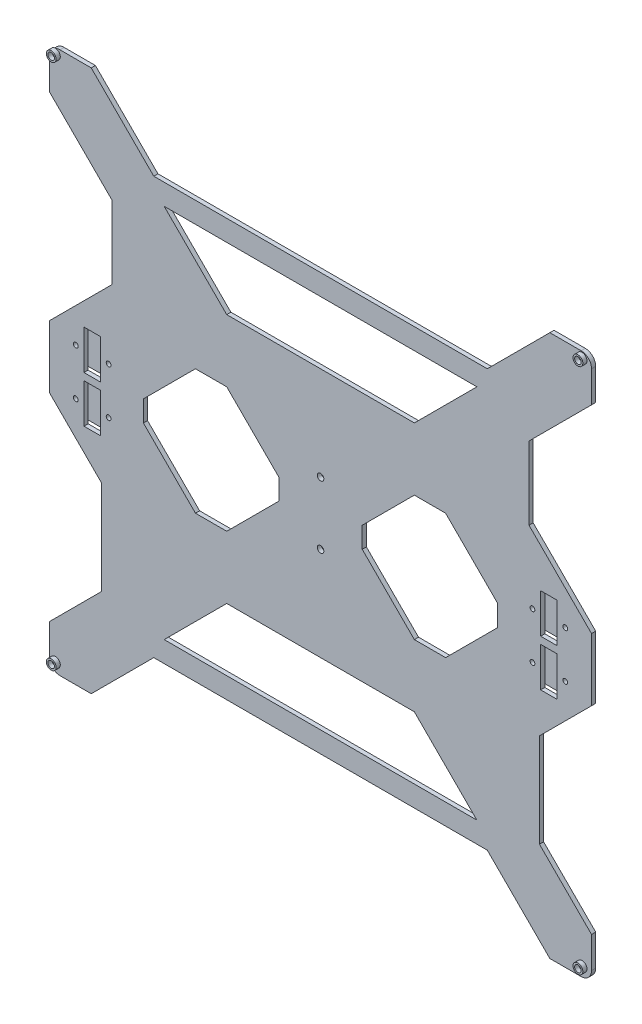
SolidWorks part; units mm, degrees
ref_plane "Front Plane" through (0, 0, 0) normal (0, 0, 1) x (1, 0, 0)
ref_plane "Top Plane" through (0, 0, 0) normal (0, 1, 0) x (1, 0, 0)
ref_plane "Right Plane" through (0, 0, 0) normal (1, 0, 0) x (0, 0, -1)
sketch "Model" plane through (0, 0, 0) normal (0, 0, 1) x (1, 0, 0)
  line L0 (38.5361, 132.6139) -> (38.5361, 132.4727)
  line L1 (38.5361, -178.6774) -> (38.5361, -178.7219)
  line L2 (-253.5639, -197.5861) -> (-253.5639, -197.7273)
  line L3 (-252.5813, 70.3317) -> (-252.5813, 25.8817)
  line L4 (-258.9313, -82.0683) -> (-258.9313, -139.2183)
  line L5 (38.5361, 132.6139) -> (38.5361, 132.4727)
  line L6 (38.5361, -178.6774) -> (38.5361, -178.7219)
  line L7 (7.7687, -139.2183) -> (7.7687, -82.0683)
  line L8 (1.4187, 25.8817) -> (1.4187, 70.3317)
  line L9 (-23.9813, 95.7317) -> (-227.1813, 95.7317)
  line L10 (-290.6813, 108.4317) -> (-252.5813, 70.3317)
  line L11 (-30.3313, -145.5683) -> (-68.4313, -107.4683)
  line L12 (-23.9813, -158.2683) -> (14.1187, -196.3683)
  line L13 (39.5187, 108.4317) -> (39.5187, 127.4817)
  line L14 (-227.1813, 95.7317) -> (-265.2813, 133.8317)
  line L15 (-220.8313, 83.0317) -> (-182.7313, 44.9317)
  line L16 (-274.6813, -45.4288) -> (-254.6813, -45.4288) construction
  line L17 (39.5187, -170.9683) -> (7.7687, -139.2183)
  line L18 (-265.2813, -196.3683) -> (-227.1813, -158.2683)
  line L19 (-182.7313, -107.4683) -> (-68.4313, -107.4683)
  line L20 (-264.6813, -45.4288) -> (-264.6813, -43.5832) construction
  line L21 (1.4187, 70.3317) -> (39.5187, 108.4317)
  line L22 (-23.9813, 95.7317) -> (14.1187, 133.8317)
  line L23 (-30.3313, 83.0317) -> (-68.4313, 44.9317)
  line L25 (-258.9313, -139.2183) -> (-290.6813, -170.9683)
  line L26 (-182.7313, 44.9317) -> (-68.4313, 44.9317)
  line L27 (-220.8313, -145.5683) -> (-182.7313, -107.4683)
  line L28 (-220.8313, -145.5683) -> (-30.3313, -145.5683)
  line L29 (-258.9313, -82.0683) -> (-290.6813, -50.3183)
  line L30 (-290.6813, -12.2183) -> (-290.6813, -50.3183)
  line L31 (-274.6813, -43.9683) -> (-274.6813, -31.2683) construction
  line L32 (-290.6813, -12.2183) -> (-252.5813, 25.8817)
  line L33 (-201.7813, -69.3683) -> (-233.5313, -37.6183)
  line L34 (-182.7313, -69.3683) -> (-201.7813, -69.3683)
  line L35 (1.4187, 25.8817) -> (39.5187, -12.2183)
  line L36 (39.5187, -12.2183) -> (39.5187, -50.3183)
  line L37 (-150.9813, -37.6183) -> (-182.7313, -69.3683)
  line L38 (39.5187, -50.3183) -> (22.4579, -67.3791)
  line L39 (22.4579, -67.3791) -> (7.7687, -82.0683)
  line L40 (-100.1813, -37.6183) -> (-100.1813, -24.9183)
  line L41 (-150.9813, -37.6183) -> (-150.9813, -24.9183)
  line L42 (-150.9813, -24.9183) -> (-182.7313, 6.8317)
  line L43 (-182.7313, 6.8317) -> (-201.7813, 6.8317)
  line L44 (-201.7813, 6.8317) -> (-233.5313, -24.9183)
  line L45 (-233.5313, -24.9183) -> (-233.5313, -37.6183)
  line L46 (-17.6313, -24.9183) -> (-17.6313, -37.6183)
  line L47 (-49.3813, 6.8317) -> (-17.6313, -24.9183)
  line L48 (-220.8313, 83.0317) -> (-30.3313, 83.0317)
  line L49 (-68.4313, 6.8317) -> (-49.3813, 6.8317)
  line L50 (-100.1813, -24.9183) -> (-68.4313, 6.8317)
  line L51 (-100.1813, -37.6183) -> (-68.4313, -69.3683)
  line L52 (-68.4313, -69.3683) -> (-49.3813, -69.3683)
  line L53 (-49.3813, -69.3683) -> (-17.6313, -37.6183)
  line L58 (-265.2813, -196.3683) -> (-284.3313, -196.3683)
  line L59 (-290.6813, -190.0183) -> (-290.6813, -170.9683)
  line L60 (-290.6813, 108.4317) -> (-290.6813, 127.4817)
  line L61 (-284.3313, 133.8317) -> (-265.2813, 133.8317)
  line L62 (14.1187, 133.8317) -> (33.1687, 133.8317)
  line L64 (39.5187, -170.9683) -> (39.5187, -190.0183)
  line L65 (33.1687, -196.3683) -> (14.1187, -196.3683)
  line L71 (-227.1813, -158.2683) -> (-23.9813, -158.2683)
  line L72 (38.5361, -178.6774) -> (38.5361, -178.7219)
  line L74 (-227.1813, -158.2683) -> (-23.9813, -158.2683)
  line L75 (38.5361, -178.6774) -> (38.5361, -178.7219)
  line L77 (-125.5813, 95.7317) -> (-125.5813, -158.2683) construction
  line L78 (-290.6813, -31.2683) -> (39.5187, -31.2683) construction
  arc A0 (33.1687, -196.3683) -> (39.5187, -190.0183) centre (33.1687, -190.0183) ccw
  arc A1 (-290.6813, -190.0183) -> (-284.3313, -196.3683) centre (-284.3313, -190.0183) ccw
  arc A2 (-290.6813, 127.4817) -> (-284.3313, 133.8317) centre (-284.3313, 127.4817) cw
  arc A3 (33.1687, 133.8317) -> (39.5187, 127.4817) centre (33.1687, 127.4817) cw
  circle A4 centre (-287.1253, -190.6025) radius 1.4605
  circle A5 centre (33.7529, -190.6025) radius 1.4605
  circle A6 centre (33.7529, 130.2757) radius 1.4605
  circle A7 centre (-287.1253, 130.2757) radius 1.4605
  circle A8 centre (-274.6813, -45.4288) radius 1.4605
  circle A9 centre (-254.6813, -45.4288) radius 1.4605
  circle A10 centre (23.5187, -45.4288) radius 1.4605
  circle A11 centre (3.5187, -45.4288) radius 1.4605
  circle A12 centre (23.5187, -17.1078) radius 1.4605
  circle A13 centre (3.5187, -17.1078) radius 1.4605
  circle A14 centre (-254.6813, -17.1078) radius 1.4605
  circle A15 centre (-274.6813, -17.1078) radius 1.4605
  circle A16 centre (-125.5813, -12.2183) radius 2
  circle A17 centre (-125.5813, -50.3183) radius 2
  point P72 (-125.5813, -31.2683)
  point P79 (-290.6813, -31.2683)
  point P114 (-125.5813, 83.0317)
  point P116 (39.5187, -31.2683)
  point P120 (-233.5313, -31.2683)
  point P129 (-150.9813, -31.2683)
  point P141 (-290.6813, -180.4933)
  point P149 (-125.5813, 44.9317)
  point P156 (-17.6313, -31.2683)
  dimension "D28" = 6.35
  dimension "D29" = 6.35
  dimension "D30" = 6.35
  dimension "D31" = 6.35
  dimension "D35" = 2.921
  dimension "D36" = 2.921
  dimension "D37" = 2.921
  dimension "D38" = 2.921
  dimension "D53" = 2.921
  dimension "D54" = 2.921
  dimension "D56" = 4
  dimension "D57" = 4
  dimension "D1" = 330.2
  dimension "D2" = 330.2
  dimension "D3" = 135
  dimension "D4" = 135
  dimension "D5" = 38.1
  dimension "D6" = 135
  dimension "D7" = 135
  dimension "D8" = 19.05
  dimension "D9" = 135
  dimension "D10" = 19.05
  dimension "D11" = 31.75
  dimension "D12" = 190.5
  dimension "D13" = 114.3
  dimension "D14" = 38.1
  dimension "D15" = 114.3
  dimension "D16" = 135
  dimension "D17" = 6.35
  dimension "D18" = 38.1
  dimension "D19" = 135
  dimension "D20" = 135
  dimension "D21" = 6.35
  dimension "D22" = 19.05
  dimension "D23" = 25.4
  dimension "D24" = 38.1
  dimension "D25" = 135
  dimension "D26" = 135
  dimension "D27" = 127
  dimension "D32" = 19.05
  dimension "D33" = 19.05
  dimension "D34" = 19.05
  dimension "D39" = 38.1
  dimension "D40" = 19.05
  dimension "D41" = 38.1
  dimension "D42" = 38.1
  dimension "D43" = 135
  dimension "D44" = 19.05
  dimension "D45" = 31.75
  dimension "D46" = 135
  dimension "D47" = 320.8782
  dimension "D48" = 320.8782
  dimension "D49" = 3.556
  dimension "D50" = 3.556
  dimension "D51" = 20
  dimension "D52" = 26
  dimension "D55" = 12.7
  dimension "D58" = 38.1
  dimension "D59" = 19.05
extrude "Boss-Extrude1" add sketch "Model" along normal mid plane 2.54 contours A3 L62 L22 L9 L14 L61 A2 L60 L10 L3 L32 L30 L29 L4 L25 L59 A1 L58 L18 L71 L12 L65 A0 L64 L17 L7 L39 L38 L36 L35 L8 L21 L13 A17 A16 A14 A13 A12 A10 A9 region at (-125.5808, -32.1456, 0)
sketch "Sketch1" plane through (0, 0, 1.27) normal (0, 0, 1) x (1, 0, 0)
  line L1 (-269.6813, -33.4288) -> (-259.6813, -33.4288)
  line L2 (-269.6813, -33.4288) -> (-269.6813, -57.4288)
  line L3 (-269.6813, -57.4288) -> (-259.6813, -57.4288)
  line L4 (-259.6813, -33.4288) -> (-259.6813, -57.4288)
  line L5 (-269.6813, -5.1078) -> (-259.6813, -5.1078)
  line L6 (-269.6813, -5.1078) -> (-269.6813, -29.1078)
  line L7 (-269.6813, -29.1078) -> (-259.6813, -29.1078)
  line L8 (-259.6813, -5.1078) -> (-259.6813, -29.1078)
  line L9 (8.5187, -5.1078) -> (18.5187, -5.1078)
  line L10 (8.5187, -5.1078) -> (8.5187, -29.1078)
  line L11 (8.5187, -29.1078) -> (18.5187, -29.1078)
  line L12 (18.5187, -5.1078) -> (18.5187, -29.1078)
  line L13 (8.5187, -33.4288) -> (18.5187, -33.4288)
  line L14 (8.5187, -33.4288) -> (8.5187, -57.4288)
  line L15 (8.5187, -57.4288) -> (18.5187, -57.4288)
  line L16 (18.5187, -33.4288) -> (18.5187, -57.4288)
  circle A1 centre (-274.6813, -45.4288) radius 1.4605 construction
  circle A5 centre (-274.6813, -17.1078) radius 1.4605 construction
  circle A7 centre (-254.6813, -17.1078) radius 1.4605 construction
  circle A8 centre (23.5187, -17.1078) radius 1.4605 construction
  circle A9 centre (23.5187, -45.4288) radius 1.4605 construction
  dimension "D3" = 12
  dimension "D4" = 5
  dimension "D5" = 10
  dimension "D8" = 12
  dimension "D11" = 12
  dimension "D15" = 12
  dimension "D1" = 10
  dimension "D2" = 24
  dimension "D6" = 24
  dimension "D7" = 5
  dimension "D9" = 24
  dimension "D10" = 5
  dimension "D12" = 10
  dimension "D13" = 10
  dimension "D14" = 24
  dimension "D16" = 5
extrude "Cut-Extrude1" cut sketch "Sketch1" against normal blind 10
sketch "Sketch2" plane through (0, 0, 1.27) normal (0, 0, 1) x (1, 0, 0)
  circle A0 centre (33.7529, -190.6025) radius 3
  circle A1 centre (33.7529, -190.6025) radius 2
  circle A2 centre (-287.1253, -190.6025) radius 2
  circle A3 centre (-287.1253, -190.6025) radius 3
  circle A4 centre (-287.1253, 130.2757) radius 2
  circle A5 centre (-287.1253, 130.2757) radius 3
  circle A6 centre (33.7529, 130.2757) radius 2
  circle A7 centre (33.7529, 130.2757) radius 3
  dimension "D1" = 6
  dimension "D2" = 4
extrude "Boss-Extrude2" add sketch "Sketch2" along normal blind 2.54
sketch "Sketch3" plane through (0, 0, -1.27) normal (0, 0, -1) x (-1, 0, 0)
  line L0 (264.6813, -5.1078) -> (264.6813, -17.1078) construction
  line L1 (254.6813, -7.1078) -> (274.6813, -7.1078)
  line L2 (254.6813, -7.1078) -> (254.6813, -27.1078)
  line L3 (254.6813, -27.1078) -> (274.6813, -27.1078)
  line L4 (274.6813, -7.1078) -> (274.6813, -27.1078)
  line L5 (254.6813, -7.1078) -> (274.6813, -27.1078) construction
  line L6 (254.6813, -27.1078) -> (274.6813, -7.1078) construction
  line L7 (254.6813, -27.1078) -> (274.6813, -27.1078)
  line L12 (254.6813, -35.4288) -> (274.6813, -35.4288)
  line L13 (113.0267, 3.6533) -> (134.9991, 3.6533)
  line L14 (113.0267, 3.6533) -> (113.0267, -64.6419)
  line L15 (113.0267, -64.6419) -> (134.9991, -64.6419)
  line L16 (134.9991, 3.6533) -> (134.9991, -64.6419)
  line L17 (113.0267, 3.6533) -> (134.9991, -64.6419) construction
  line L18 (113.0267, -64.6419) -> (134.9991, 3.6533) construction
  line L19 (-23.5187, -7.1078) -> (-3.5187, -7.1078)
  line L20 (-23.5187, -7.1078) -> (-23.5187, -27.1078)
  line L22 (-3.5187, -7.1078) -> (-3.5187, -27.1078)
  line L23 (-23.5187, -7.1078) -> (-3.5187, -27.1078) construction
  line L24 (-23.5187, -27.1078) -> (-3.5187, -7.1078) construction
  line L29 (-3.5187, -27.1078) -> (-23.5187, -27.1078)
  line L30 (254.6813, -35.4288) -> (254.6813, -55.4288)
  line L31 (259.6813, -5.1078) -> (269.6813, -5.1078) construction
  line L32 (264.6813, -17.1078) -> (269.6813, -17.1078) construction
  line L33 (269.6813, -5.1078) -> (269.6813, -29.1078) construction
  line L34 (264.6813, -33.4288) -> (264.6813, -45.4288) construction
  line L35 (259.6813, -33.4288) -> (269.6813, -33.4288) construction
  line L36 (264.6813, -45.4288) -> (269.6813, -45.4288) construction
  line L37 (269.6813, -33.4288) -> (269.6813, -57.4288) construction
  line L38 (-13.5187, -5.1078) -> (-13.5187, -17.1078) construction
  line L39 (-18.5187, -5.1078) -> (-8.5187, -5.1078) construction
  line L40 (-13.5187, -17.1078) -> (-8.5187, -17.1078) construction
  line L41 (-8.5187, -5.1078) -> (-8.5187, -29.1078) construction
  line L42 (-13.5187, -33.4288) -> (-13.5187, -45.4288) construction
  line L43 (-18.5187, -33.4288) -> (-8.5187, -33.4288) construction
  line L44 (-13.5187, -45.4288) -> (-8.5187, -45.4288) construction
  line L45 (-8.5187, -33.4288) -> (-8.5187, -57.4288) construction
  line L46 (-23.5187, -35.4288) -> (-3.5187, -35.4288)
  line L47 (-23.5187, -35.4288) -> (-23.5187, -55.4288)
  line L48 (-23.5187, -55.4288) -> (-3.5187, -55.4288)
  line L49 (-3.5187, -35.4288) -> (-3.5187, -55.4288)
  line L50 (-23.5187, -35.4288) -> (-3.5187, -55.4288) construction
  line L51 (-23.5187, -55.4288) -> (-3.5187, -35.4288) construction
  line L52 (254.6813, -55.4288) -> (274.6813, -55.4288)
  line L53 (274.6813, -35.4288) -> (274.6813, -55.4288)
  line L54 (254.6813, -35.4288) -> (274.6813, -55.4288) construction
  line L55 (254.6813, -55.4288) -> (274.6813, -35.4288) construction
  point P0 (264.6813, -17.1078)
  point P5 (264.6813, -45.4288)
  point P8 (124.0129, -30.4943)
  point P13 (-13.5187, -17.1078)
  point P18 (-13.5187, -45.4288)
  dimension "D1" = 20
  dimension "D2" = 20
  dimension "D3" = 20
  dimension "D4" = 20
  dimension "D5" = 20
  dimension "D6" = 20
  dimension "D7" = 20
  dimension "D8" = 20
extrude "Boss-Extrude3" add sketch "Sketch3" along normal blind 1 contours L29 L22 L19 L20 | L49 L46 L47 L48 | L4 L1 L2 L3 | L53 L12 L30 L52 | L16 L13 L14 L15 region at (-264.6813, -17.1078, -1.27) region at (-264.6813, -45.4288, -1.27) region at (-124.0129, -30.4943, -1.27) region at (13.5187, -17.1078, -1.27) region at (13.5187, -45.4288, -1.27)
